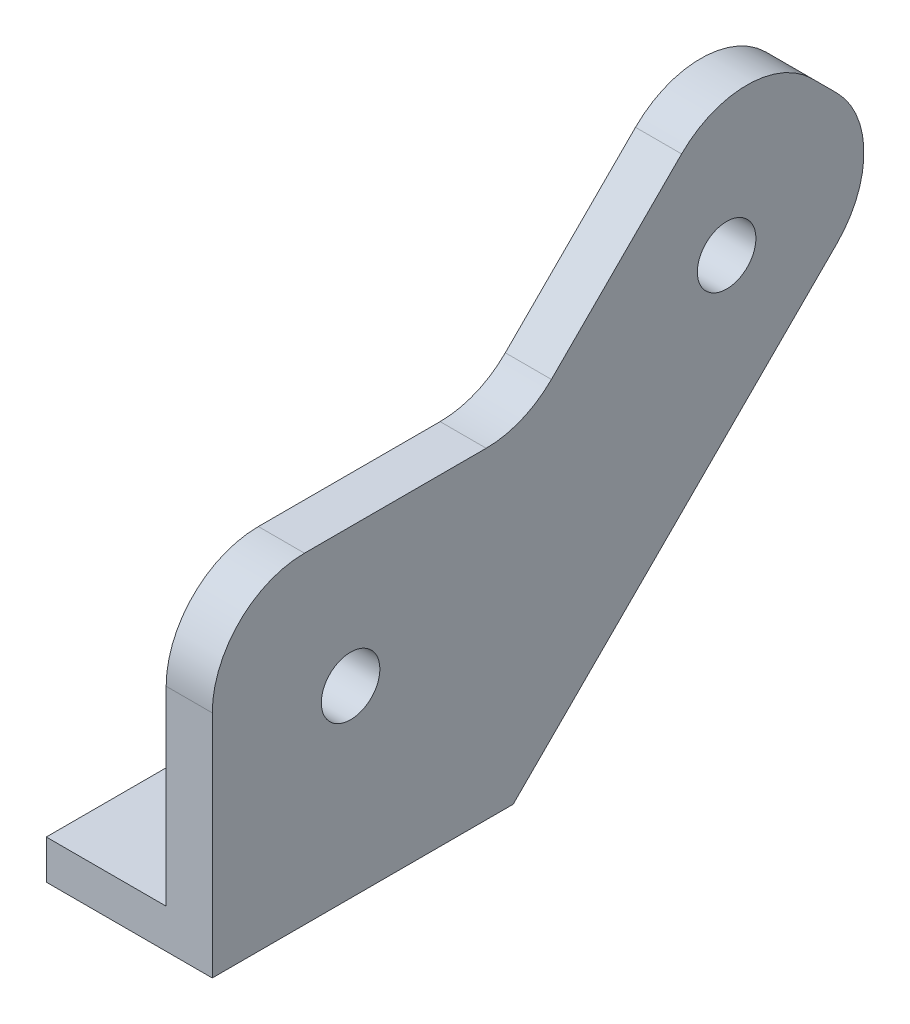
SolidWorks part; units mm, degrees
ref_plane "Front Plane" through (0, 0, 0) normal (0, 0, 1) x (1, 0, 0)
ref_plane "Top Plane" through (0, 0, 0) normal (0, 1, 0) x (1, 0, 0)
ref_plane "Right Plane" through (0, 0, 0) normal (1, 0, 0) x (0, 0, -1)
sketch "Sketch1" plane through (0, 0, 0) normal (1, 0, 0) x (0, 0, -1)
  line L0 (69.9001, 0) -> (-62.5182, 0) construction
  line L1 (-9.5152, 19.93) -> (65.4385, 19.93) construction
  line L2 (-9.5152, 19.93) -> (-9.5152, 56.8817) construction
  line L3 (8.1143, 0) -> (-24.5152, 0)
  line L4 (-24.5152, 0) -> (-24.5152, 24.8988)
  line L5 (-14.5152, 34.8988) -> (5.1919, 34.8988)
  line L6 (12.263, 37.8277) -> (26.3806, 51.9453)
  line L7 (40.5227, 51.9453) -> (43.2201, 49.2479)
  line L8 (43.2201, 35.1058) -> (8.1143, 0)
  line L9 (12.263, 37.8277) -> (24.4131, 37.8277) construction
  line L10 (22.8451, 48.4097) -> (39.6845, 31.5703) construction
  circle A0 centre (31.2648, 39.99) radius 3.175
  circle A1 centre (-9.5152, 19.93) radius 3.175
  arc A2 (-24.5152, 24.8988) -> (-14.5152, 34.8988) centre (-14.5152, 24.8988) cw
  arc A3 (12.263, 37.8277) -> (5.1919, 34.8988) centre (5.1919, 44.8988) cw
  arc A4 (43.2201, 35.1058) -> (43.2201, 49.2479) centre (36.149, 42.1769) ccw
  arc A5 (40.5227, 51.9453) -> (26.3806, 51.9453) centre (33.4517, 44.8742) ccw
  point P26 (31.2648, 39.99)
  dimension "D1" = 6.35
  dimension "D2" = 6.35
  dimension "D6" = 10
  dimension "D7" = 10
  dimension "D8" = 10
  dimension "D3" = 19.93
  dimension "D4" = 40.78
  dimension "D5" = 20.06
  dimension "D9" = 15
  dimension "D10" = 15
  dimension "D11" = 45
extrude "Extrude body" add sketch "Sketch1" along normal blind 5
sketch "Sketch2" plane through (0, 0, 0) normal (1, 0, 0) x (0, 0, -1)
  line L12 (-21.5152, 24.8988) -> (-21.5152, 3)
  line L13 (-21.5152, 3) -> (6.8717, 3)
  line L14 (6.8717, 3) -> (41.0988, 37.2271)
  line L15 (41.0988, 47.1266) -> (38.4014, 49.824)
  line L16 (28.5019, 49.824) -> (14.3843, 35.7064)
  line L17 (5.1919, 31.8988) -> (-14.5152, 31.8988)
  line L18 (-21.5152, 24.8988) -> (-21.5152, 3)
  line L19 (-21.5152, 3) -> (6.8717, 3)
  line L20 (6.8717, 3) -> (41.0988, 37.2271)
  line L21 (41.0988, 47.1266) -> (38.4014, 49.824)
  line L22 (28.5019, 49.824) -> (14.3843, 35.7064)
  line L23 (5.1919, 31.8988) -> (-14.5152, 31.8988)
  arc A8 (-14.5152, 31.8988) -> (-21.5152, 24.8988) centre (-14.5152, 24.8988) ccw
  arc A9 (41.0988, 37.2271) -> (41.0988, 47.1266) centre (36.149, 42.1769) ccw
  arc A10 (38.4014, 49.824) -> (28.5019, 49.824) centre (33.4517, 44.8742) ccw
  arc A11 (5.1919, 31.8988) -> (14.3843, 35.7064) centre (5.1919, 44.8988) ccw
  arc A12 (-14.5152, 31.8988) -> (-21.5152, 24.8988) centre (-14.5152, 24.8988) ccw
  arc A13 (41.0988, 37.2271) -> (41.0988, 47.1266) centre (36.149, 42.1769) ccw
  arc A14 (38.4014, 49.824) -> (28.5019, 49.824) centre (33.4517, 44.8742) ccw
  arc A15 (5.1919, 31.8988) -> (14.3843, 35.7064) centre (5.1919, 44.8988) ccw
  dimension "D1" = 3
extrude "Inset body" cut sketch "Sketch2" along normal blind 2
sketch "Sketch3" plane through (2, 0, 0) normal (-1, 0, 0) x (0, 0, 1)
  circle A0 centre (9.5152, 19.93) radius 6.175
  circle A1 centre (-31.2648, 39.99) radius 6.175
  circle A2 centre (9.5152, 19.93) radius 3.175 construction
  circle A3 centre (-31.2648, 39.99) radius 3.175 construction
  dimension "D1" = 3
  dimension "D2" = 3
extrude "Cut hole boss" add sketch "Sketch3" along normal blind 5
sketch "Ream hole" plane through (0, 0, 0) normal (-1, 0, 0) x (0, 0, 1)
  circle A0 centre (-31.2648, 39.99) radius 3.175
  circle A1 centre (9.5152, 19.93) radius 3.175
extrude "Cut-Extrude2" cut sketch "Ream hole" along normal through all and the other way blind 5
sketch "Sketch4" plane through (2, 0, 0) normal (-1, 0, 0) x (0, 0, 1)
  line L0 (-6.8717, 3) -> (-41.0988, 37.2271) construction
  line L1 (-8.1143, 0) -> (24.5152, 0)
  line L2 (-8.1143, 0) -> (-8.1143, 4.2426)
  line L3 (-8.1143, 4.2426) -> (24.5152, 4.2426)
  line L4 (24.5152, 0) -> (24.5152, 4.2426)
  line L5 (24.5152, 24.8988) -> (24.5152, 0) construction
extrude "Boss-Extrude1" add sketch "Sketch4" along normal blind 15
hole_wizard "CSK for M3 Flat Head Machine Screw1" positions "Sketch6" profile "Sketch5" countersink size "M3" standard "ANSI Metric" end condition through all
sketch "Sketch6" plane through (0, 4.2426, 0) normal (0, 1, 0) x (1, 0, 0)
  line L1 (-13, 8.1143) -> (0, 8.1143) construction
  line L2 (-6.5, 8.1143) -> (-6.5, -24.5152) construction
  line L3 (-13, -24.5152) -> (0, -24.5152) construction
  line L5 (-13, -24.5152) -> (-13, 8.1143) construction
  line L6 (-13, -8.2005) -> (2, -8.2005) construction
  line L7 (2, -21.5152) -> (2, 8.1143) construction
  point P0 (-6.5, -8.2005)
sketch "Sketch5" plane through (-6.5, 4.2426, 8.2005) normal (1, 0, 0) x (0, 0, 1)
  line L0 (0, 0) -> (0, 4.2426)
  line L1 (0, 4.2426) -> (1.7, 4.2426)
  line L2 (1.7, 4.2426) -> (1.7, 1.45)
  line L3 (1.7, 1.45) -> (3.15, 0)
  line L5 (3.15, 0) -> (0, 0)
  line L6 (-1.7, 1.45) -> (-3.15, 0) construction
  line L11 (0, -6.35) -> (0, 107.95) construction
  dimension "Thru Hole Dia." = 3.4
  dimension "Thru Hole Depth" = 4.2426
  dimension "Near C'Sink Dia." = 6.3
  dimension "Near C'Sink Angle" = 90
